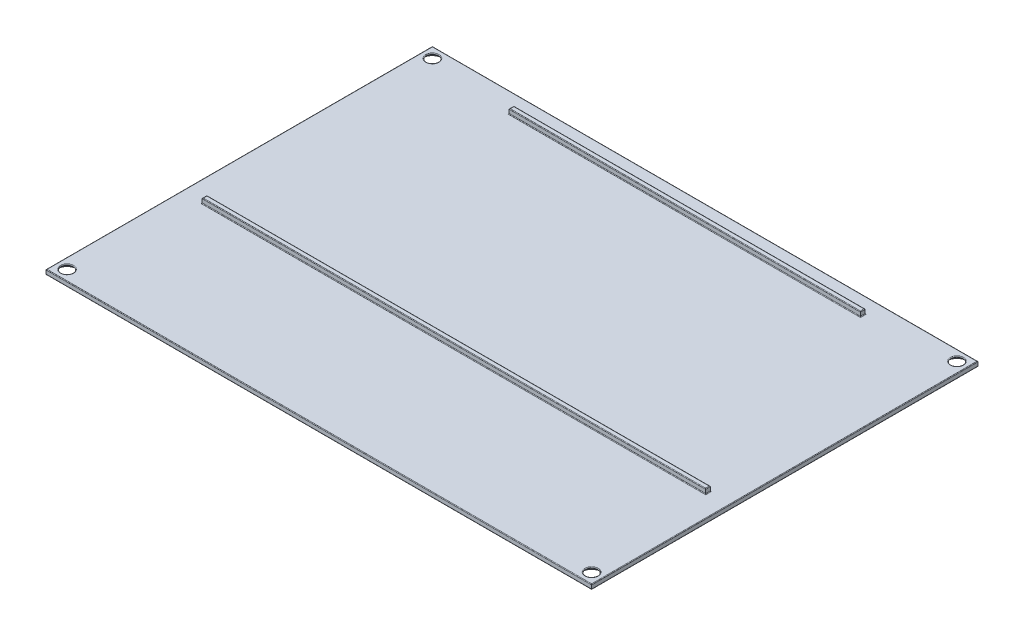
SolidWorks part; units mm, degrees
ref_plane "Front Plane" through (0, 0, 0) normal (0, 0, 1) x (1, 0, 0)
ref_plane "Top Plane" through (0, 0, 0) normal (0, 1, 0) x (1, 0, 0)
ref_plane "Right Plane" through (0, 0, 0) normal (1, 0, 0) x (0, 0, -1)
sketch "Sketch1" plane through (0, 0, 0) normal (0, 1, 0) x (1, 0, 0)
  line L0 (-116.5, 48) -> (-107.5, 48)
  line L1 (107.5, -48) -> (-107.5, -48) construction
  line L2 (107.5, -48) -> (107.5, 48) construction
  line L3 (107.5, 48) -> (-107.5, 48) construction
  line L4 (-107.5, -48) -> (-107.5, 48) construction
  line L5 (107.5, -48) -> (-107.5, 48) construction
  line L6 (107.5, 48) -> (-107.5, -48) construction
  line L7 (-116.5, 57) -> (116.5, 57)
  line L8 (-116.5, 57) -> (-116.5, -108)
  line L9 (-116.5, -108) -> (116.5, -108)
  line L10 (116.5, 57) -> (116.5, -108)
  line L11 (-107.5, 48) -> (-107.5, 57)
  line L12 (-116.5, -99) -> (-107.5, -99)
  line L13 (-107.5, -99) -> (-107.5, -108)
  line L14 (107.5, -108) -> (107.5, -99)
  line L15 (107.5, -99) -> (116.5, -99)
  line L16 (116.5, 48) -> (107.5, 48)
  line L17 (107.5, 48) -> (107.5, 57)
  line L18 (0, -48) -> (0, -108) construction
  line L19 (-107.5, 48) -> (-116.5, 57) construction
  line L20 (107.5, 48) -> (116.5, 57) construction
  line L21 (-107.5, -99) -> (-116.5, -108) construction
  line L22 (107.5, -99) -> (116.5, -108) construction
  line L23 (-107.5, -48) -> (-107.5, -48.3)
  line L24 (107.5, -48) -> (107.5, -48.3) construction
  line L25 (0, 48.3) -> (0, 48) construction
  line L26 (-107.5, -48.3) -> (107.5, -48.3)
  line L27 (-107.5, -48.3) -> (-107.5, -50.3)
  line L28 (-107.5, -50.3) -> (107.5, -50.3)
  line L29 (107.5, -48.3) -> (107.5, -50.3)
  line L30 (-75, 50.3) -> (75, 50.3)
  line L31 (-75, 50.3) -> (-75, 48.3)
  line L32 (-75, 48.3) -> (75, 48.3)
  line L33 (75, 50.3) -> (75, 48.3)
  circle A0 centre (-112, 52.5) radius 1.75
  circle A1 centre (112, 52.5) radius 1.75
  circle A2 centre (112, -103.5) radius 1.75
  circle A3 centre (-112, -103.5) radius 1.75
  point P0 (0, 0)
  point P35 (0, 48)
  dimension "D1" = 9
  dimension "D3" = 3.5
  dimension "D5" = 2
  dimension "D2" = 60
  dimension "D4" = 0.3
  dimension "D6" = 215
  dimension "D7" = 96
  dimension "D8" = 2
  dimension "D9" = 150
  dimension "D10" = 0.3
extrude "Boss-Extrude1" add sketch "Sketch1" against normal blind 2 contours L16 L17 L7 L11 L0 L8 L12 L13 L9 L14 L15 L10 | L15 L14 L9 L10 A2 | L17 L16 L10 L7 A1 | L13 L12 L8 L9 A3 | L0 L11 L7 L8 A0 region at (-116.3727, 0, -52.5) region at (0, 0, 25.8264) region at (-112, 0, 99.1273) region at (112, 0, -56.8727) region at (107.6273, 0, 103.5)
extrude "Boss-Extrude2" add sketch "Sketch1<3>" along normal mid plane 4 contours L33 L30 L31 L32 | L29 L26 L27 L28 region at (0, 0, 49.3) region at (0, 0, -49.3)
sketch "Sketch1<3>" plane through (0, 0, 0) normal (0, 1, 0) x (1, 0, 0) same geometry as "Sketch1"
chamfer "Chamfer1" distance 2.5 angle 45 4 edges at (112, -2, 105.25) (-112, -2, 105.25) (-112, -2, -50.75) (112, -2, -50.75)
fillet "Fillet1" radius 0.25 32 edges at (0, 2, -48.3) (-75, 2, -49.3) (0, 2, -50.3) (75, 2, -49.3) (0, 2, 50.3) (-107.5, 2, 49.3) (0, 2, 48.3) (107.5, 2, 49.3) (-75, 0, -49.3) (0, 0, -48.3) (75, 0, -49.3) (0, 0, -50.3) (0, 0, 50.3) (107.5, 0, 49.3) (0, 0, 48.3) (-107.5, 0, 49.3) (116.5, 0, 25.5) (0, 0, 108) (-116.5, 0, 25.5) (0, 0, -57) (112, 0, -50.25) (-112, 0, -50.25) (-112, 0, 105.75) (112, 0, 105.75) (-116.5, -2, 25.5) (0, -2, 108) (116.5, -2, 25.5) (0, -2, -57) (112, -2, -48.25) (-112, -2, -48.25) (-112, -2, 107.75) (112, -2, 107.75)
